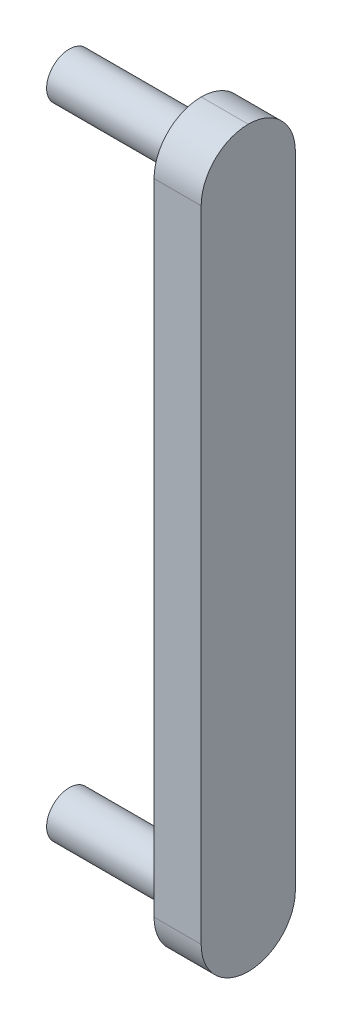
SolidWorks part; units mm, degrees
ref_plane "Front Plane" through (0, 0, 0) normal (0, 0, 1) x (1, 0, 0)
ref_plane "Top Plane" through (0, 0, 0) normal (0, 1, 0) x (1, 0, 0)
ref_plane "Right Plane" through (0, 0, 0) normal (1, 0, 0) x (0, 0, -1)
sketch "Sketch1" plane through (0, 0, 0) normal (1, 0, 0) x (0, 0, -1)
  line L1 (3.175, -24.7269) -> (-3.175, -24.7269)
  line L2 (3.175, -24.7269) -> (3.175, 24.7269)
  line L3 (3.175, 24.7269) -> (-3.175, 24.7269)
  line L4 (-3.175, -24.7269) -> (-3.175, 24.7269)
  line L5 (3.175, -24.7269) -> (-3.175, 24.7269) construction
  line L6 (3.175, 24.7269) -> (-3.175, -24.7269) construction
  point P0 (0, 0)
  dimension "D1" = 49.4538
  dimension "D2" = 6.35
extrude "Boss-Extrude1" add sketch "Sketch1" along normal blind 3.175
sketch "Sketch2" plane through (0, 0, 0) normal (-1, 0, 0) x (0, 0, 1)
  line L0 (-3.175, 24.7269) -> (3.175, 24.7269) construction
  line L1 (-3.175, -24.7269) -> (-3.175, 24.7269) construction
  line L2 (3.175, -24.7269) -> (-3.175, -24.7269) construction
  line L3 (3.175, 24.7269) -> (3.175, -24.7269) construction
  circle A0 centre (0, 21.5519) radius 1.524
  circle A1 centre (0, -21.5519) radius 1.524
  dimension "D1" = 3.048
  dimension "D6" = 3.048
  dimension "D2" = 3.175
  dimension "D3" = 3.175
  dimension "D4" = 3.175
  dimension "D5" = 3.175
extrude "Boss-Extrude2" add sketch "Sketch2" along normal blind 8.89
fillet "Fillet1" radius 3.175 4 edges at (1.5875, -24.7269, 3.175) (1.5875, -24.7269, -3.175) (1.5875, 24.7269, -3.175) (1.5875, 24.7269, 3.175)
